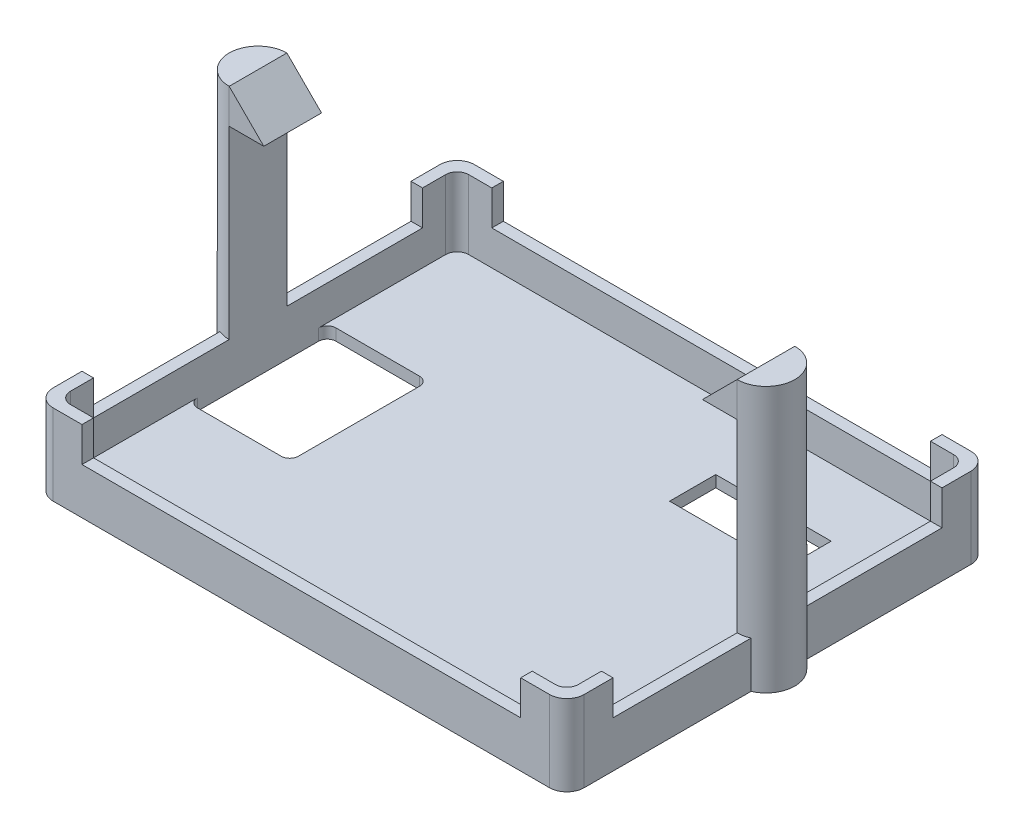
SolidWorks part; units mm, degrees
note: The reader was unsure of these and kept them because the rebuilt part matched: shared geometry of "Sketch1<3>", "Sketch1<4>", "Sketch1<6>", "Sketch1<9>".
ref_plane "Front Plane" through (0, 0, 0) normal (0, 0, 1) x (1, 0, 0)
ref_plane "Top Plane" through (0, 0, 0) normal (0, 1, 0) x (1, 0, 0)
ref_plane "Right Plane" through (0, 0, 0) normal (1, 0, 0) x (0, 0, -1)
sketch "Sketch1" plane through (0, 0, 0) normal (0, 1, 0) x (1, 0, 0)
  line L0 (0, 17.25) -> (44, 17.25) construction
  line L1 (1, 0) -> (43, 0)
  line L2 (0, 12) -> (0, 22.5)
  line L3 (1, 34.5) -> (43, 34.5)
  line L4 (44, 1) -> (44, 33.5)
  line L5 (0.5, -1) -> (43.5, -1)
  line L6 (-1, 0.5) -> (-1, 34)
  line L7 (0.5, 35.5) -> (43.5, 35.5)
  line L8 (45, 0.5) -> (45, 34)
  line L9 (0.75, 24) -> (8.25, 24)
  line L10 (8, 23.25) -> (0.75, 23.25)
  line L11 (8.75, 22.5) -> (8.75, 12)
  line L12 (8, 11.25) -> (0.75, 11.25)
  line L13 (0, 1) -> (0, 9.75)
  line L14 (0, 24.75) -> (0, 33.5)
  line L15 (0, 24.75) -> (0, 22.5)
  line L16 (9.5, 22.75) -> (9.5, 11.75)
  line L17 (8.25, 10.5) -> (0.75, 10.5)
  line L18 (0, 12) -> (0, 9.75)
  line L19 (3, 35.5) -> (3, 34.5)
  line L20 (-1, 31.5) -> (0, 31.5)
  line L21 (44, 31.5) -> (45, 31.5)
  line L22 (41, 34.5) -> (41, 35.5)
  line L23 (41, 0) -> (41, -1)
  line L24 (3, 0) -> (3, -1)
  line L25 (0, 3) -> (-1, 3)
  line L26 (28.2, 28.7) -> (38.2, 28.7)
  line L27 (28.2, 28.7) -> (28.2, 24.7)
  line L28 (28.2, 24.7) -> (38.2, 24.7)
  line L29 (38.2, 28.7) -> (38.2, 24.7)
  line L30 (44, 3) -> (45, 3)
  arc A0 (0, 1) -> (1, 0) centre (1, 1) ccw
  arc A1 (43, 0) -> (44, 1) centre (43, 1) ccw
  arc A2 (44, 33.5) -> (43, 34.5) centre (43, 33.5) ccw
  arc A3 (1, 34.5) -> (0, 33.5) centre (1, 33.5) ccw
  arc A4 (0.5, -1) -> (-1, 0.5) centre (0.5, 0.5) cw
  arc A5 (-1, 34) -> (0.5, 35.5) centre (0.5, 34) cw
  arc A6 (43.5, -1) -> (45, 0.5) centre (43.5, 0.5) ccw
  arc A7 (43.5, 35.5) -> (45, 34) centre (43.5, 34) cw
  arc A8 (9.5, 11.75) -> (8.25, 10.5) centre (8.25, 11.75) cw
  arc A9 (9.5, 22.75) -> (8.25, 24) centre (8.25, 22.75) ccw
  arc A10 (0.75, 23.25) -> (0, 22.5) centre (0.75, 22.5) ccw
  arc A11 (0, 12) -> (0.75, 11.25) centre (0.75, 12) ccw
  arc A12 (8.75, 12) -> (8, 11.25) centre (8, 12) cw
  arc A13 (8, 23.25) -> (8.75, 22.5) centre (8, 22.5) cw
  arc A14 (0.75, 24) -> (0, 24.75) centre (0.75, 24.75) cw
  arc A15 (0.75, 10.5) -> (0, 9.75) centre (0.75, 9.75) ccw
  arc A16 (44, 19.75) -> (44, 14.75) centre (44, 17.25) cw
  arc A17 (0, 19.75) -> (0, 14.75) centre (0, 17.25) ccw
  point P7 (0, 0)
  point P10 (44, 0)
  point P13 (44, 34.5)
  point P22 (-1, -1)
  point P27 (45, -1)
  point P30 (45, 35.5)
  point P33 (4, 17.25)
  point P36 (0, 24)
  point P44 (9.5, 10.5)
  point P47 (9.5, 24)
  point P61 (0, 10.5)
  dimension "D3" = 0.75
  dimension "D6" = 10
  dimension "D5" = 5.8
  dimension "D2" = 0.75
  dimension "D1" = 7.25
  dimension "D9" = 3
  dimension "D4" = 0.75
  dimension "D7" = 4
  dimension "D8" = 5.8
  dimension "D10" = 3
  dimension "D11" = 3
  dimension "D12" = 3
extrude "Boss-Extrude1" add sketch "Sketch1" along normal blind 1
extrude "Boss-Extrude2" add sketch "Sketch1<3>" along normal blind 4 contours A7 L7 A5 L6 A4 L5 A6 L8 A3 L3 A2 L4 A1 L1 A0 L13 L18 L2 L15 L14 | A4 L5 L24 L1 A0 L13 L25 L6 | L1 L24 L5 L23 | L5 A6 L8 L30 L4 A1 L1 L23 | L8 A16 L4 L30 | L4 A16 L8 L21 | A16 L4 L8 | A7 L7 L22 L3 A2 L4 L21 L8 | L3 L22 L7 L19 | A5 L6 L20 L14 A3 L3 L19 L7 | A17 L6 L25 L13 L18 L2 | A17 L2 L15 L14 L20 L6
sketch "Sketch1<3>" plane through (0, 0, 0) normal (0, 1, 0) x (1, 0, 0) same geometry as "Sketch1"
extrude "Boss-Extrude3" add sketch "Sketch1<4>" along normal blind 23 contours A16 L8 | A16 L4 L8
sketch "Sketch1<4>" plane through (0, 0, 0) normal (0, 1, 0) x (1, 0, 0) same geometry as "Sketch1"
sketch "Sketch2" plane through (44, 0, 0) normal (-1, 0, 0) x (0, 0, 1)
  line L0 (-14.75, 23) -> (-14.75, 4) construction
  line L1 (-19.75, 23) -> (-14.75, 23)
  line L2 (-19.75, 23) -> (-19.75, 20)
  line L3 (-19.75, 20) -> (-14.75, 20)
  line L4 (-14.75, 23) -> (-14.75, 20)
  dimension "D1" = 3
extrude "Boss-Extrude4" add sketch "Sketch2" along normal blind 3
sketch "Sketch3" plane through (0, 0, -14.75) normal (0, 0, 1) x (1, 0, 0)
  line L0 (41, 20) -> (44, 23)
  line L1 (44, 23) -> (41, 23)
  line L2 (41, 23) -> (41, 20)
extrude "Cut-Extrude1" cut sketch "Sketch3" against normal through all contours L1 L2 L0
extrude "Boss-Extrude5" add sketch "Sketch1<6>" along normal blind 7 contours A5 L6 L20 L14 A3 L3 L19 L7 | A4 L5 L24 L1 A0 L13 L25 L6 | L5 A6 L8 L30 L4 A1 L1 L23 | A7 L7 L22 L3 A2 L4 L21 L8
sketch "Sketch1<6>" plane through (0, 0, 0) normal (0, 1, 0) x (1, 0, 0) same geometry as "Sketch1"
extrude "Boss-Extrude8" add sketch "Sketch1<9>" along normal blind 23 contours L6 A17 | L2 A17 L6
sketch "Sketch1<9>" plane through (0, 0, 0) normal (0, 1, 0) x (1, 0, 0) same geometry as "Sketch1"
sketch "Sketch6" plane through (0, 0, 0) normal (1, 0, 0) x (0, 0, -1)
  line L0 (19.75, 23) -> (19.75, 4) construction
  line L1 (14.75, 23) -> (19.75, 23)
  line L2 (14.75, 23) -> (14.75, 20)
  line L3 (14.75, 20) -> (19.75, 20)
  line L4 (19.75, 23) -> (19.75, 20)
  dimension "D1" = 3
extrude "Boss-Extrude9" add sketch "Sketch6" along normal blind 3
sketch "Sketch7" plane through (0, 0, -14.75) normal (0, 0, 1) x (1, 0, 0)
  line L0 (3, 23) -> (3, 20)
  line L1 (3, 20) -> (0, 23)
  line L2 (0, 23) -> (3, 23)
extrude "Cut-Extrude3" cut sketch "Sketch7" against normal through all
